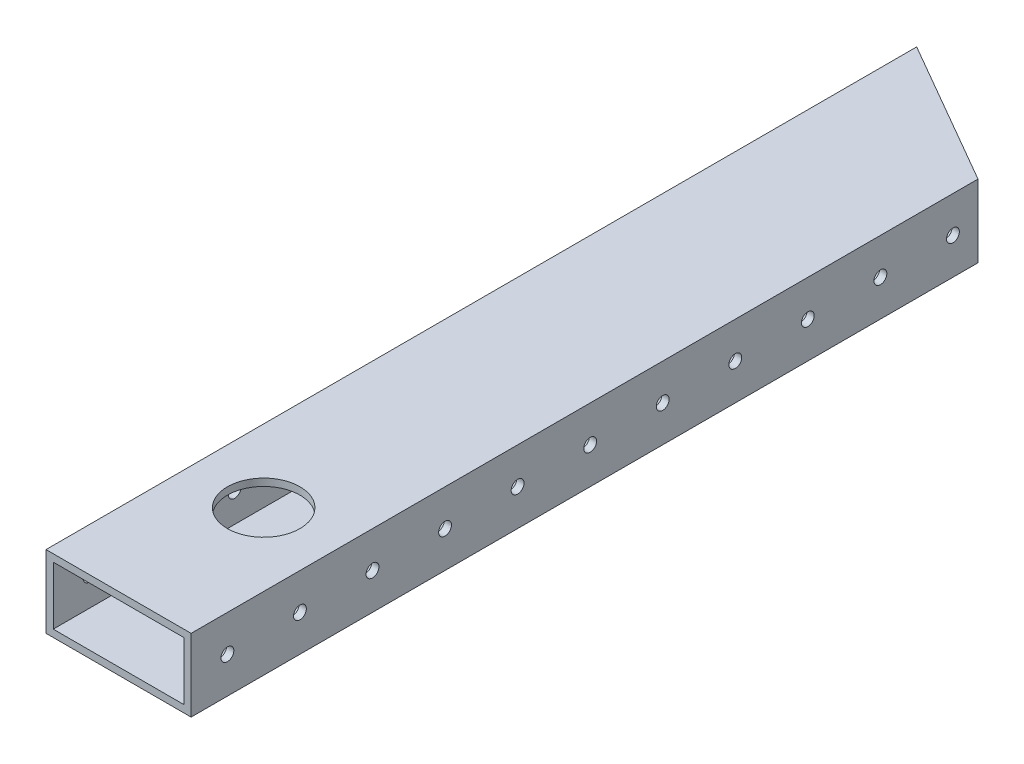
SolidWorks part; units mm, degrees
ref_plane "Front Plane" through (0, 0, 0) normal (0, 0, 1) x (1, 0, 0)
ref_plane "Top Plane" through (0, 0, 0) normal (0, 1, 0) x (1, 0, 0)
ref_plane "Right Plane" through (0, 0, 0) normal (1, 0, 0) x (0, 0, -1)
sketch "Sketch1" plane through (0, 0, 0) normal (0, 0, 1) x (1, 0, 0)
  line L1 (-25.4, -12.7) -> (25.4, -12.7)
  line L2 (-25.4, -12.7) -> (-25.4, 12.7)
  line L3 (-25.4, 12.7) -> (25.4, 12.7)
  line L4 (25.4, -12.7) -> (25.4, 12.7)
  line L5 (-25.4, -12.7) -> (25.4, 12.7) construction
  line L6 (-25.4, 12.7) -> (25.4, -12.7) construction
  line L7 (-22.86, -10.16) -> (22.86, -10.16)
  line L8 (-22.86, -10.16) -> (-22.86, 10.16)
  line L9 (-22.86, 10.16) -> (22.86, 10.16)
  line L10 (22.86, -10.16) -> (22.86, 10.16)
  line L11 (-22.86, -10.16) -> (22.86, 10.16) construction
  line L12 (-22.86, 10.16) -> (22.86, -10.16) construction
  point P0 (0, 0)
  point P6 (0, 0)
  dimension "D1" = 50.8
  dimension "D2" = 25.4
  dimension "D3" = 2.54
  dimension "D4" = 2.54
extrude "Boss-Extrude1" add sketch "Sketch1" against normal blind 355.6
hole_wizard "#8 Clearance Hole1" positions "Sketch2" profile "Sketch3" hole size "#8" standard "ANSI Inch" end condition through all
sketch "Sketch2" plane through (25.4, 0, 0) normal (1, 0, 0) x (0, 0, -1)
  line L0 (355.6, -12.7) -> (0, -12.7) construction
  point P0 (12.7, 0)
  point P16 (38.1, 0)
  point P17 (63.5, 0)
  point P18 (88.9, 0)
  point P19 (114.3, 0)
  point P20 (139.7, 0)
  point P21 (165.1, 0)
  point P22 (190.5, 0)
  point P23 (215.9, 0)
  point P24 (241.3, 0)
  point P25 (266.7, 0)
  point P26 (292.1, 0)
  point P27 (317.5, 0)
  point P28 (342.9, 0)
  dimension "D1" = 12.7
  dimension "D2" = 12.7
  dimension "D3" = 14
sketch "Sketch3" plane through (25.4, 0, -12.7) normal (0, 1, 0) x (0, 0, -1)
  line L0 (0, 0) -> (0, 50.8)
  line L1 (0, 50.8) -> (2.2479, 50.8)
  line L2 (2.2479, 50.8) -> (2.2479, 0)
  line L5 (2.2479, 0) -> (0, 0)
  line L11 (0, -6.35) -> (0, 107.95) construction
  dimension "Thru Hole Dia." = 4.4958
  dimension "Thru Hole Depth" = 50.8
hole_wizard "1 (1) Diameter Hole1" positions "Sketch6" profile "Sketch7" hole size "1" standard "ANSI Inch" end condition through all
sketch "Sketch6" plane through (0, 12.7, 0) normal (0, 1, 0) x (1, 0, 0)
  line L0 (25.4, 355.6) -> (25.4, 0) construction
  line L1 (25.4, 0) -> (-25.4, 0) construction
  point P0 (0, 101.6)
  dimension "D1" = 25.4
  dimension "D2" = 101.6
sketch "Sketch7" plane through (0, 12.7, -101.6) normal (1, 0, 0) x (0, 0, 1)
  line L0 (0, 0) -> (0, 25.4)
  line L1 (0, 25.4) -> (12.7, 25.4)
  line L2 (12.7, 25.4) -> (12.7, 0)
  line L5 (12.7, 0) -> (0, 0)
  line L11 (0, -6.35) -> (0, 107.95) construction
  dimension "Thru Hole Dia." = 25.4
  dimension "Thru Hole Depth" = 25.4
sketch "Sketch8" plane through (0, 12.7, 0) normal (0, 1, 0) x (1, 0, 0)
  line L0 (25.4, 0) -> (25.4, 50.8)
  line L1 (25.4, 355.6) -> (25.4, 0) construction
  line L2 (25.4, 50.8) -> (60.3179, 50.8)
  line L3 (60.3179, 50.8) -> (60.3179, -5.2193)
  line L4 (60.3179, -5.2193) -> (-35.9606, -5.2193)
  line L5 (-35.9606, -5.2193) -> (-35.9606, 50.8)
  line L6 (-35.9606, 50.8) -> (25.4, 50.8)
  line M3 (-25.4, 0) -> (25.4, 0)
  line M4 (25.4, 0) -> (25.4, 355.6)
  line M6 (-25.4, 355.6) -> (-25.4, 0)
  dimension "D1" = 50.8
extrude "Cut-Extrude1" cut sketch "Sketch8" against normal blind 71.882 and the other way blind 421.64 contours L6 M6 M3 M4 region at (0, 12.7, -25.4)
sketch "Sketch12" plane through (0, -12.7, 0) normal (0, -1, 0) x (1, 0, 0)
  line L0 (-25.4, -355.6) -> (25.4, -326.2706)
  line L1 (25.4, -355.6) -> (25.4, -50.8) construction
  line L2 (25.4, -326.2706) -> (25.4, -355.6)
  line L3 (-25.4, -355.6) -> (25.4, -355.6) construction
  line L4 (25.4, -355.6) -> (-25.4, -355.6)
  dimension "D1" = 30
extrude "Cut-Extrude6" cut sketch "Sketch12" against normal blind 494.792
